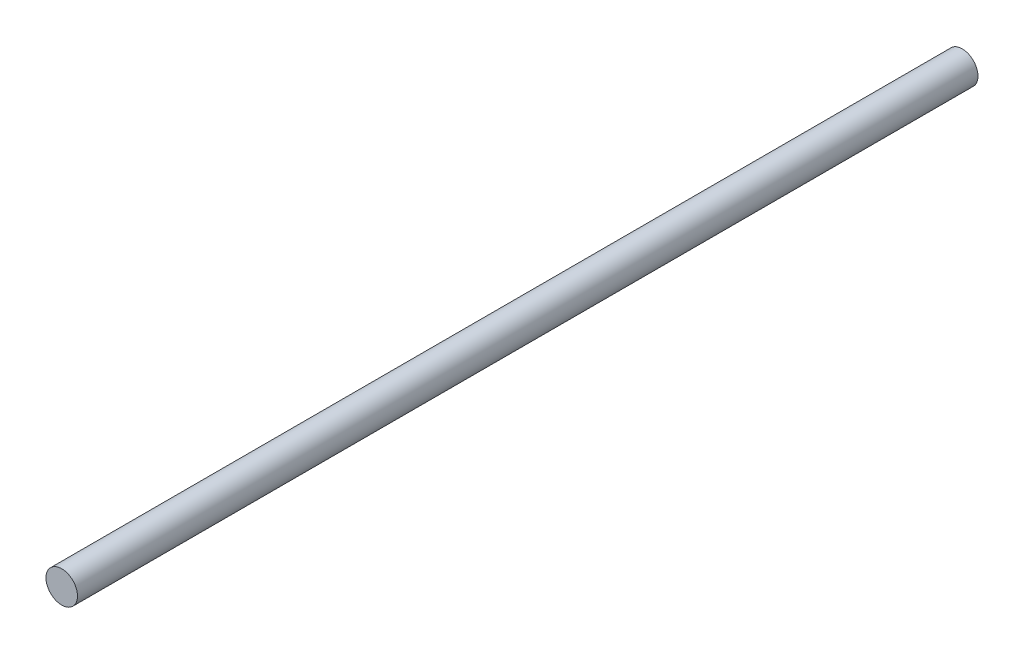
SolidWorks part; units mm, degrees
ref_plane "Front Plane" through (0, 0, 0) normal (0, 0, 1) x (1, 0, 0)
ref_plane "Top Plane" through (0, 0, 0) normal (0, 1, 0) x (1, 0, 0)
ref_plane "Right Plane" through (0, 0, 0) normal (1, 0, 0) x (0, 0, -1)
sketch "Sketch1" plane through (0, 0, 0) normal (0, 0, 1) x (1, 0, 0)
  circle A0 centre (0, 0) radius 3.1115
  dimension "D1" = 6.223
extrude "Boss-Extrude1" add sketch "Sketch1" along normal blind 177.8
